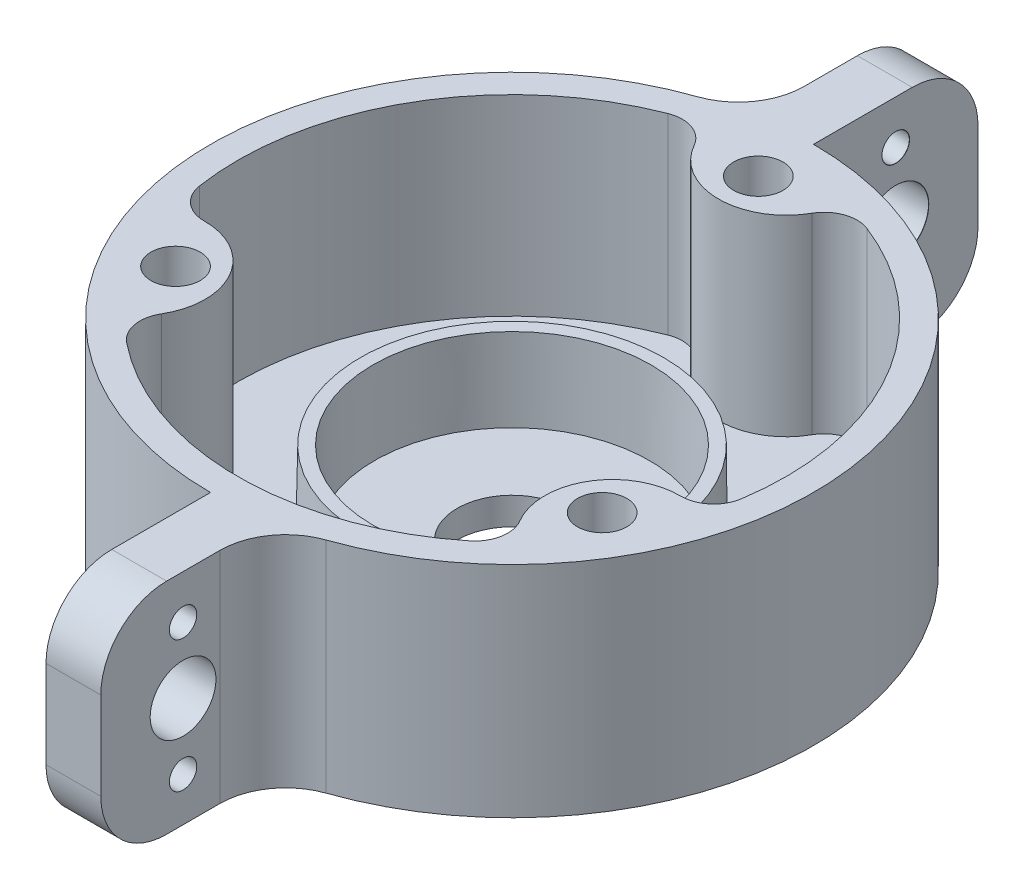
SolidWorks part; units mm, degrees
note: The reader was unsure of these and kept them because the rebuilt part matched: shared geometry of "Sketch1<2>", "Sketch1<4>".
material "1060 Alloy"
ref_plane "Front Plane" through (0, 0, 0) normal (0, 0, 1) x (1, 0, 0)
ref_plane "Top Plane" through (0, 0, 0) normal (0, 1, 0) x (1, 0, 0)
ref_plane "Right Plane" through (0, 0, 0) normal (1, 0, 0) x (0, 0, -1)
sketch "Sketch1" plane through (0, 0, 0) normal (0, 1, 0) x (1, 0, 0)
  circle A0 centre (0, 0) radius 50
  circle A1 centre (0, 0) radius 55
  circle A2 centre (0, 0) radius 10
  circle A3 centre (0, 0) radius 25
  circle A4 centre (0, 0) radius 28
  dimension "D1" = 100
  dimension "D2" = 5
  dimension "D3" = 20
  dimension "D4" = 3
  dimension "D5" = 50
extrude "Boss-Extrude1" add sketch "Sketch1" along normal blind 40 contours A1 A0
extrude "Boss-Extrude2" add sketch "Sketch1<2>" along normal blind 5 contours A0 | A4 A3 | A3 A2
sketch "Sketch1<2>" plane through (0, 0, 0) normal (0, 1, 0) x (1, 0, 0) same geometry as "Sketch1"
extrude "Boss-Extrude8" add sketch "Sketch1<4>" along normal blind 20 draft 1 contours A4 A3
sketch "Sketch1<4>" plane through (0, 0, 0) normal (0, 1, 0) x (1, 0, 0) same geometry as "Sketch1"
sketch "Sketch2" plane through (0, 5, 0) normal (0, 1, 0) x (1, 0, 0)
  line L0 (0, 0) -> (0, 20.1041) construction
  line L1 (0, 0) -> (79.3623, 0) construction
  circle A1 centre (0, 0) radius 50 construction
  circle A2 centre (0, 0) radius 50 construction
  arc A4 (-12.2205, 48.4836) -> (12.2205, 48.4836) centre (0, 50) ccw
  arc A5 (-12.2205, 48.4836) -> (12.2205, 48.4836) centre (0, 0) cw
  circle A6 centre (0, 44.9259) radius 4.5
  point P10 (0, 50)
  point P14 (-12.2205, 48.4836)
  point P15 (0, 44.9259)
  point P16 (0, 0)
  dimension "D1" = 9
extrude "Boss-Extrude3" add sketch "Sketch2" along normal up to surface (35 mm away)
fillet "Fillet1" radius 6 2 edges at (12.2205, 22.5, -48.4836) (-12.2205, 22.5, -48.4836)
pattern_circular "CirPattern1" count 3 over 360 about axis through (0, 0, 0) along (0, 1, 0) of "Boss-Extrude3", "Fillet1"
sketch "Sketch3" plane through (0, 0, 0) normal (0, -1, 0) x (1, 0, 0)
  line L0 (0, -55) -> (0, -85)
  line L1 (0, -85) -> (-10, -85)
  line L2 (-10, -85) -> (-10, -54.0833)
  circle A0 centre (0, 0) radius 55 construction
  arc A1 (0, -55) -> (-10, -54.0833) centre (0, 0) cw
  point P10 (-9.9427, -78.4581)
  dimension "D1" = 10
  dimension "D2" = 30
extrude "Boss-Extrude7" add sketch "Sketch3" against normal up to surface (40 mm away) up to face at (0, 40, 0)
fillet "Fillet2" radius 12 1 edges at (-10, 20, -54.0833)
hole_wizard "Ø5.0mm Dowel Hole1" positions "Sketch4" profile "Sketch6" hole size "Ø5.0" standard "ISO" end condition through all
sketch "Sketch4" plane through (0, 0, 0) normal (1, 0, 0) x (0, 0, -1)
  line L0 (70, 40) -> (70, 0) construction
  line L1 (85, 40) -> (55, 40) construction
  line L2 (85, 0) -> (55, 0) construction
  line L4 (70, 20) -> (80.3035, 20) construction
  point P0 (70, 32)
  point P2 (70, 8)
  point P19 (70, 8.4478)
  point P20 (70, 31.9269)
  point P21 (70, 40)
  point P22 (70, 20)
  point P23 (70, 7.9482)
  dimension "D1" = 24
sketch "Sketch6" plane through (0, 32, -70) normal (0, 1, 0) x (0, 0, -1)
  line L0 (0, 0) -> (0, 55)
  line L1 (0, 55) -> (2.5, 55)
  line L2 (2.5, 55) -> (2.5, 0.025)
  line L3 (2.5, 0.025) -> (2.525, 0)
  line L5 (2.525, 0) -> (0, 0)
  line L6 (-2.5, 0.025) -> (-2.525, 0) construction
  line L11 (0, -6.35) -> (0, 107.95) construction
  dimension "Thru Hole Dia." = 5
  dimension "Thru Hole Depth" = 55
  dimension "Near C'Sink Dia." = 5.05
  dimension "Near C'Sink Angle" = 90
hole_wizard "Ø12.0mm Dowel Hole1" positions "Sketch9" profile "Sketch10" hole size "Ø12.0" standard "ISO" end condition through all
sketch "Sketch9" plane through (0, 0, 0) normal (1, 0, 0) x (0, 0, -1)
  point P0 (70, 20)
sketch "Sketch10" plane through (0, 20, -70) normal (0, 1, 0) x (0, 0, -1)
  line L0 (0, 0) -> (0, 55)
  line L1 (0, 55) -> (6, 55)
  line L2 (6, 55) -> (6, 0.025)
  line L3 (6, 0.025) -> (6.025, 0)
  line L5 (6.025, 0) -> (0, 0)
  line L6 (-6, 0.025) -> (-6.025, 0) construction
  line L11 (0, -6.35) -> (0, 107.95) construction
  dimension "Thru Hole Dia." = 12
  dimension "Thru Hole Depth" = 55
  dimension "Near C'Sink Dia." = 12.05
  dimension "Near C'Sink Angle" = 90
fillet "Fillet3" radius 12 2 edges at (-5, 40, -85) (-5, 0, -85)
pattern_circular "CirPattern2" count 2 over 360 about axis through (0, 0, 0) along (0, 1, 0) of "Boss-Extrude7", "Fillet2", "Ø5.0mm Dowel Hole1", "Ø12.0mm Dowel Hole1", "Fillet3"
